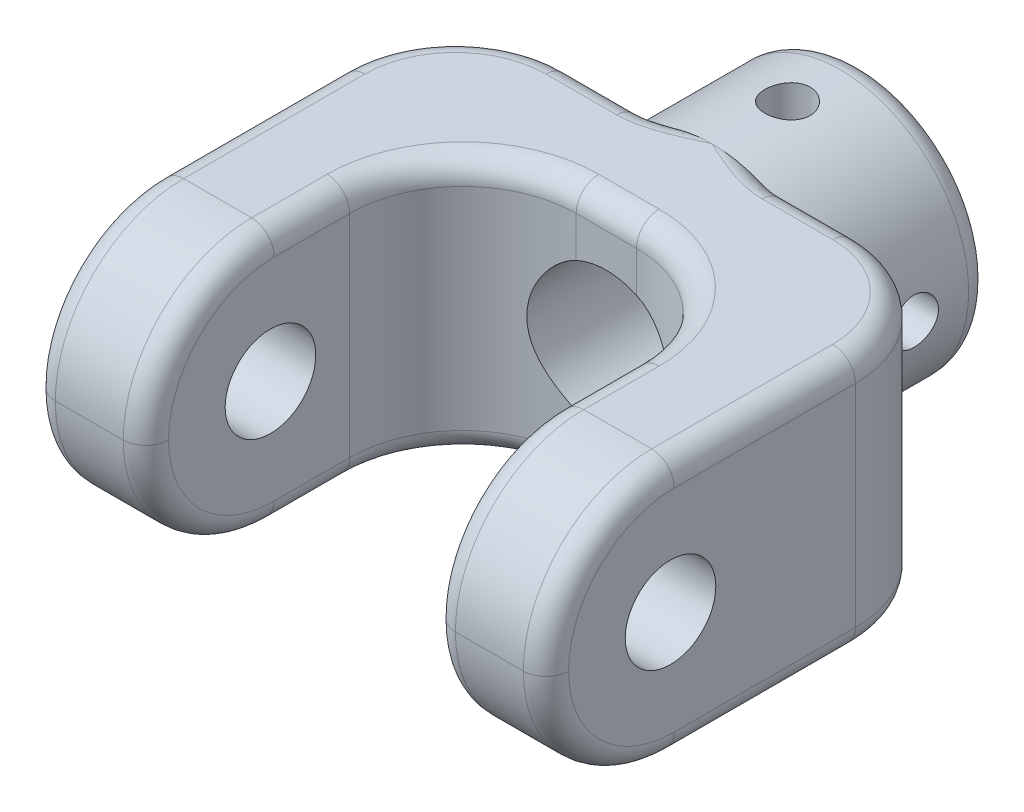
SolidWorks part; units mm, degrees
material "Gray Cast Iron"
ref_plane "Front Plane" through (0, 0, 0) normal (0, 0, 1) x (1, 0, 0)
ref_plane "Top Plane" through (0, 0, 0) normal (0, 1, 0) x (1, 0, 0)
ref_plane "Right Plane" through (0, 0, 0) normal (1, 0, 0) x (0, 0, -1)
sketch "Sketch1" plane through (0, 0, 0) normal (0, 0, 1) x (1, 0, 0)
  circle A0 centre (0, 0) radius 9.5
  circle A1 centre (0, 0) radius 17
  dimension "D1" = 34
  dimension "D2" = 19
extrude "Boss-Extrude1" add sketch "Sketch1" along normal blind 20
sketch "Sketch3" plane through (0, 0, 0) normal (0, 1, 0) x (1, 0, 0)
  line L0 (-34, -20) -> (34, -20)
  line L1 (34, -20) -> (34, -76)
  line L2 (34, -76) -> (19, -76)
  line L3 (19, -76) -> (19, -34)
  line L4 (19, -34) -> (-19, -34)
  line L5 (-19, -34) -> (-19, -76)
  line L6 (-19, -76) -> (-34, -76)
  line L7 (-34, -76) -> (-34, -20)
  line L8 (-17, -20) -> (17, -20) construction
  dimension "D1" = 68
  dimension "D2" = 14
  dimension "D3" = 56
  dimension "D4" = 0
  dimension "D5" = 90
  dimension "56" = 56
  dimension "D6" = 90
  dimension "D7" = 15
  dimension "D8" = 15
  dimension "D9" = 19
extrude "Boss-Extrude2" add sketch "Sketch3" along normal mid plane 34
fillet "Fillet1" radius 17 4 edges at (26.5, -17, 76) (26.5, 17, 76) (-26.5, -17, 76) (-26.5, 17, 76)
fillet "Fillet2" radius 3 1 edges at (17, 0, 0)
fillet "Fillet3" radius 15 4 edges at (34, 0, 20) (-19, 0, 34) (19, 0, 34) (-34, 0, 20)
fillet "Fillet4" radius 3 30 edges at (34, 12.0208, 71.0208) (34, -12.0208, 71.0208) (34, -17, 47) (29.6066, -17, 24.3934) (9.5, -17, 20) (-9.5, -17, 20) (-29.6066, -17, 24.3934) (-34, -17, 47) (-34, -12.0208, 71.0208) (-34, 12.0208, 71.0208) (-34, 17, 47) (-29.6066, 17, 24.3934) (-9.5, 17, 20) (9.5, 17, 20) (29.6066, 17, 24.3934) (34, 17, 47) (14.6066, 17, 38.3934) (0, 17, 34) (-14.6066, 17, 38.3934) (-19, 17, 54) (-19, 12.0208, 71.0208) (-19, -12.0208, 71.0208) (-19, -17, 54) (-14.6066, -17, 38.3934) (0, -17, 34) (14.6066, -17, 38.3934) (19, -17, 54) (19, -12.0208, 71.0208) (19, 12.0208, 71.0208) (19, 17, 54)
sketch "Sketch4" plane through (34, 0, 0) normal (1, 0, 0) x (0, 0, -1)
  circle A0 centre (-59.5, 0) radius 6
  dimension "D1" = 16.5
extrude "Cut-Extrude1" cut sketch "Sketch4" against normal through all both and the other way through all
sketch "Sketch5" plane through (0, 17, 0) normal (0, 1, 0) x (1, 0, 0)
  line L0 (-17, -3) -> (-17, -20) construction
  line L2 (9.5, 0) -> (-9.5, 0) construction
  circle A0 centre (0, -10) radius 3
  dimension "D1" = 17
  dimension "D2" = 10
extrude "Cut-Extrude2" cut sketch "Sketch5" against normal blind 34
sketch "Sketch6" plane through (0, 0, 20) normal (0, 0, -1) x (-1, 0, 0)
  circle A0 centre (0, 0) radius 9.5
extrude "Cut-Extrude3" cut sketch "Sketch6" against normal blind 34
pattern_circular "CirPattern1" count 4 over 360 about axis through (0, 0, 20) along (0, 0, -1) of "Cut-Extrude2" reverse direction yes
